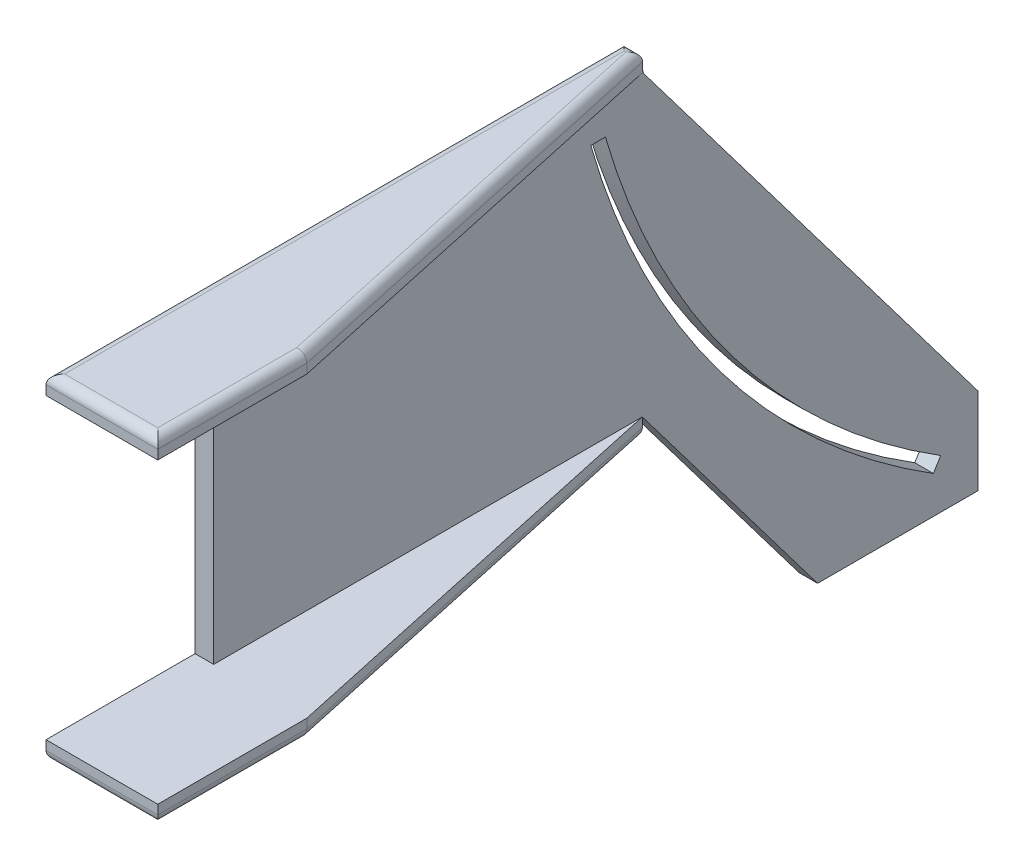
SolidWorks part; units mm, degrees
ref_plane "Front Plane" through (0, 0, 0) normal (0, 0, 1) x (1, 0, 0)
ref_plane "Top Plane" through (0, 0, 0) normal (0, 1, 0) x (1, 0, 0)
ref_plane "Right Plane" through (0, 0, 0) normal (1, 0, 0) x (0, 0, -1)
sketch "Sketch1" plane through (0, 0, 0) normal (1, 0, 0) x (0, 0, -1)
  line L0 (-129.391, -36.576) -> (-126.9146, -36.576)
  line L1 (-71.0224, -114.1738) -> (-69.7646, -112.1518)
  line L2 (-120.5646, -30.226) -> (-63.4146, -105.8018)
  line L3 (-193.675, -30.226) -> (-120.5646, -30.226)
  line L4 (-193.675, -30.226) -> (-193.675, -81.026)
  line L5 (-90.7526, -120.5238) -> (-63.4146, -120.5238)
  line L6 (-63.4146, -105.8018) -> (-63.4146, -120.5238)
  line L7 (-193.675, -81.026) -> (-120.6206, -81.026)
  line L8 (-120.6206, -81.026) -> (-90.7526, -120.5238)
  arc A0 (-126.9146, -36.576) -> (-69.7646, -112.1518) centre (0, 0) ccw
  arc A1 (-129.391, -36.576) -> (-71.0224, -114.1738) centre (0, 0) ccw
  point P2 (-123.5541, -83.1641)
  point P11 (-117.5825, -81.026)
  point P14 (-128.1528, -36.576)
  point P15 (-123.5541, -81.026)
  dimension "D1" = 132.08
  dimension "D2" = 2.3813
  dimension "D3" = 193.675
  dimension "D4" = 6.35
  dimension "D5" = 6.35
  dimension "D6" = 6.35
  dimension "D7" = 6.35
  dimension "D8" = 6.35
  dimension "D9" = 57.15
  dimension "D10" = 30.226
  dimension "D11" = 0
  dimension "D12" = 50.8
extrude "Boss-Extrude1" add sketch "Sketch1" along normal blind 3.175
sketch "Sketch2" plane through (0, -30.226, 0) normal (0, 1, 0) x (1, 0, 0)
  line L0 (3.175, -193.675) -> (0, -193.675) construction
  line L1 (0, -120.5646) -> (3.175, -120.5646)
  line L2 (0, -120.5646) -> (0, -219.075)
  line L3 (0, -219.075) -> (19.05, -219.075)
  line L4 (19.05, -193.675) -> (19.05, -219.075)
  line L5 (3.175, -120.5646) -> (19.05, -193.675)
  point P8 (1.5875, -193.675)
  dimension "D1" = 25.4
  dimension "D2" = 19.05
  dimension "D3" = 0
extrude "Boss-Extrude2" add sketch "Sketch2" along normal blind 3.175
fillet "Fillet1" radius 1.5875 6 edges at (1.5875, -27.051, 120.5646) (0, -27.051, 169.8198) (9.525, -27.051, 219.075) (19.05, -27.051, 206.375) (11.1125, -27.051, 157.1198) (1.5875, -30.226, 120.5646)
sketch "Sketch4" plane through (0, -81.026, 0) normal (0, -1, 0) x (1, 0, 0)
  line L0 (0, 120.6206) -> (3.175, 120.6206)
  line L1 (3.175, 120.6206) -> (19.05, 193.675)
  line L2 (19.05, 193.675) -> (19.05, 219.075)
  line L3 (19.05, 219.075) -> (0, 219.075)
  line L4 (0, 219.075) -> (0, 120.6206)
extrude "Boss-Extrude3" add sketch "Sketch4" along normal blind 3.175
fillet "Fillet2" radius 1.5875 5 edges at (9.525, -84.201, 219.075) (19.05, -84.201, 206.375) (11.1125, -84.201, 157.1478) (1.5875, -84.201, 120.6206) (0, -84.201, 169.8478)
